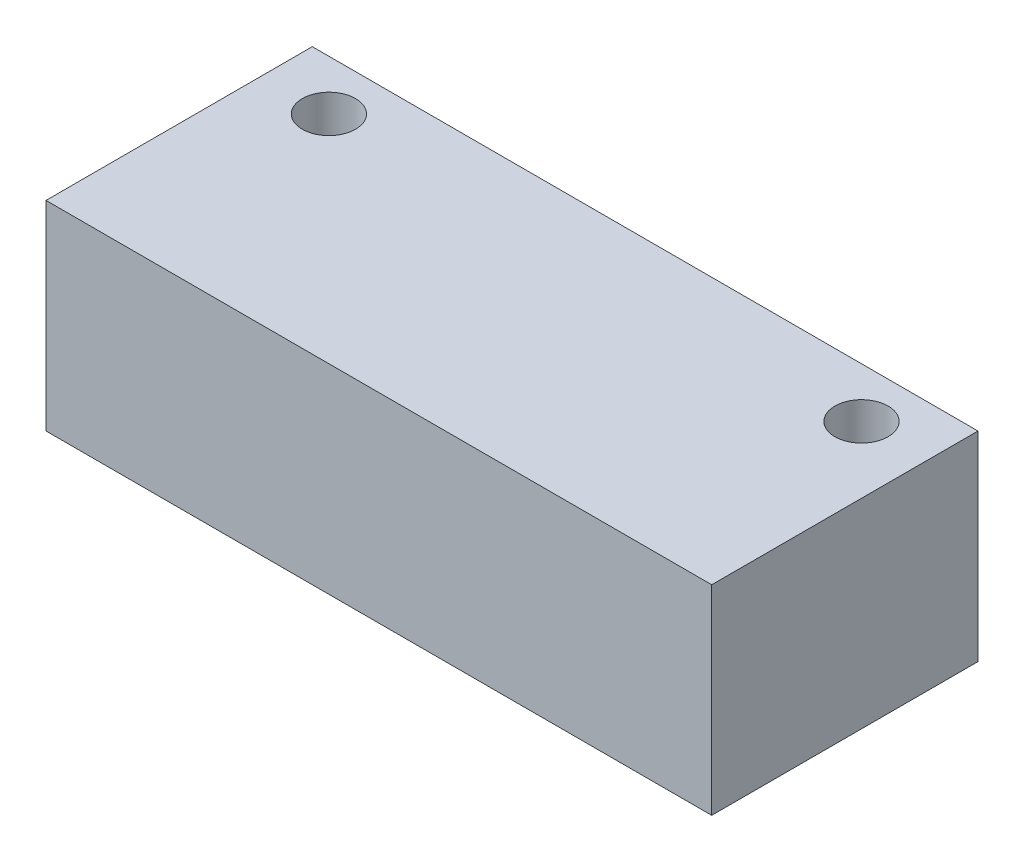
SolidWorks part; units mm, degrees
ref_plane "Front Plane" through (0, 0, 0) normal (0, 0, 1) x (1, 0, 0)
ref_plane "Top Plane" through (0, 0, 0) normal (0, 1, 0) x (1, 0, 0)
ref_plane "Right Plane" through (0, 0, 0) normal (1, 0, 0) x (0, 0, -1)
sketch "Sketch1" plane through (0, 0, 0) normal (0, 0, 1) x (1, 0, 0)
  line L1 (-20, -6) -> (20, -6)
  line L2 (-20, -6) -> (-20, 6)
  line L3 (-20, 6) -> (20, 6)
  line L4 (20, -6) -> (20, 6)
  line L5 (-20, -6) -> (20, 6) construction
  line L6 (-20, 6) -> (20, -6) construction
  point P0 (0, 0)
  dimension "D1" = 12
  dimension "D2" = 40
extrude "Boss-Extrude1" add sketch "Sketch1" along normal blind 16
sketch "Sketch2" plane through (0, -6, 0) normal (0, -1, 0) x (1, 0, 0)
  line L0 (-16, 3) -> (16, 3) construction
  line L1 (0, 0) -> (0, 3) construction
  circle A0 centre (-16, 3) radius 1.6
  circle A1 centre (16, 3) radius 1.6
  dimension "D1" = 3.2
  dimension "D2" = 32
  dimension "D3" = 3
extrude "Cut-Extrude1" cut sketch "Sketch2" against normal through all
